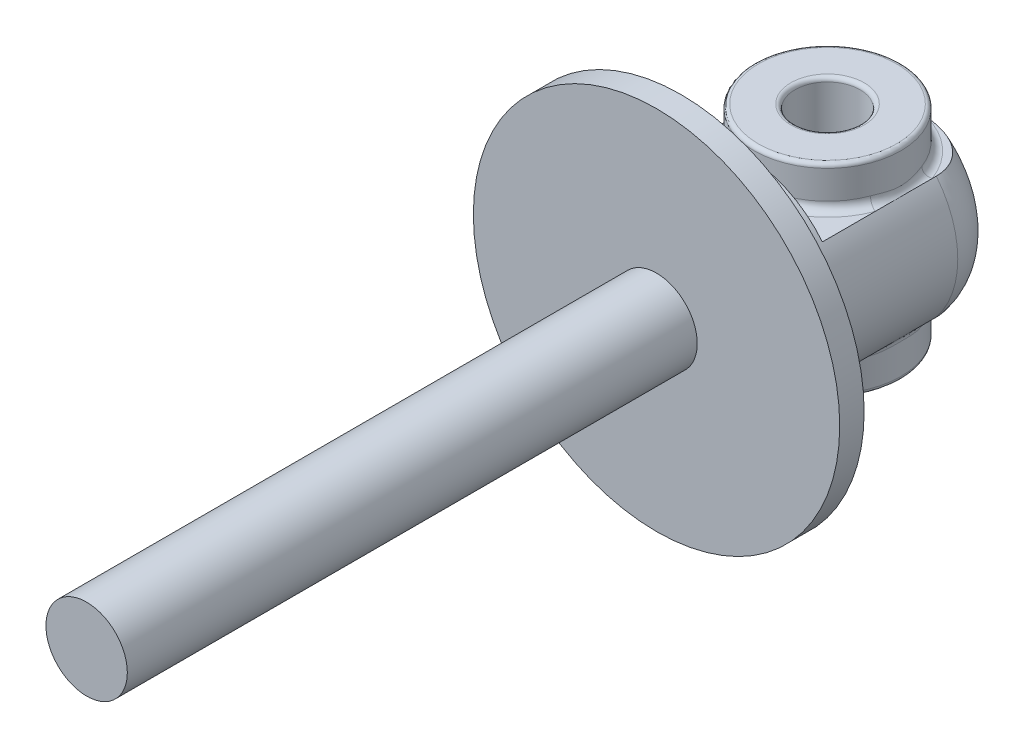
SolidWorks part; units mm, degrees
ref_plane "Piano frontale" through (0, 0, 0) normal (0, 0, 1) x (1, 0, 0)
ref_plane "Piano superiore" through (0, 0, 0) normal (0, 1, 0) x (1, 0, 0)
ref_plane "Piano destro" through (0, 0, 0) normal (1, 0, 0) x (0, 0, -1)
sketch "Sketch1" plane through (0, 0, 0) normal (0, 0, 1) x (1, 0, 0)
  circle A0 centre (0, 0) radius 22.5
  dimension "D1" = 45
extrude "Boss-Extrude1" add sketch "Sketch1" along normal blind 3
sketch "Sketch2" plane through (0, 0, 3) normal (0, 0, 1) x (1, 0, 0)
  circle A0 centre (0, 0) radius 5
  dimension "D1" = 10
extrude "Boss-Extrude2" add sketch "Sketch2" along normal blind 70
sketch "Sketch3" plane through (0, 0, 0) normal (0, 0, -1) x (-1, 0, 0)
  circle A0 centre (0, 0) radius 12
  dimension "D1" = 24
extrude "Boss-Extrude3" add sketch "Sketch3" along normal blind 28
fillet "Fillet1" radius 6 1 edges at (-12, 0, -28)
sketch "Sketch4" plane through (0, 0, 0) normal (1, 0, 0) x (0, 0, -1)
  line L0 (0, 0) -> (28, 0) construction
  line L1 (28, -6) -> (28, 6) construction
  line L2 (28, 7.5) -> (28, 27.07)
  line L3 (28, 27.07) -> (8, 27.07)
  line L4 (8, 27.07) -> (8, 7.5)
  line L5 (8, 7.5) -> (28, 7.5)
  line L6 (28, -7.5) -> (28, -27.07)
  line L7 (8, -7.5) -> (28, -7.5)
  line L8 (8, -27.07) -> (8, -7.5)
  line L9 (28, -27.07) -> (8, -27.07)
  dimension "D1" = 15
  dimension "D2" = 20
  dimension "D3" = 19.57
extrude "Cut-Extrude1" cut sketch "Sketch4" against normal through all both and the other way through all
sketch "Sketch5" plane through (0, 7.5, 0) normal (0, 1, 0) x (1, 0, 0)
  line L0 (0, 0) -> (0, 28) construction
  line L1 (6, 28) -> (-6, 28) construction
  circle A0 centre (0, 18) radius 4
  dimension "D1" = 8
  dimension "D2" = 10
extrude "Cut-Extrude2" cut sketch "Sketch5" against normal through all both and the other way through all
sketch "Sketch6" plane through (0, 7.5, 0) normal (0, 1, 0) x (1, 0, 0)
  circle A0 centre (0, 18) radius 9
  circle A1 centre (0, 18) radius 4 construction
  circle A2 centre (0, 18) radius 4
  dimension "D1" = 18
sketch "Sketch7" plane through (0, 0, 0) normal (0, 1, 0) x (1, 0, 0)
  circle A0 centre (0, 18) radius 4 construction
  circle A1 centre (0, 18) radius 4
  circle A2 centre (0, 18) radius 9 construction
  circle A3 centre (0, 18) radius 9
extrude "Boss-Extrude4" add sketch "Sketch7" along normal mid plane 25
fillet "Fillet2" radius 1 2 edges at (0, 7.5, -27) (0, -7.5, -9)
fillet "Fillet3" radius 0.5 4 edges at (0, 12.5, -14) (0, -12.5, -14) (0, -12.5, -9) (0, 12.5, -9)
